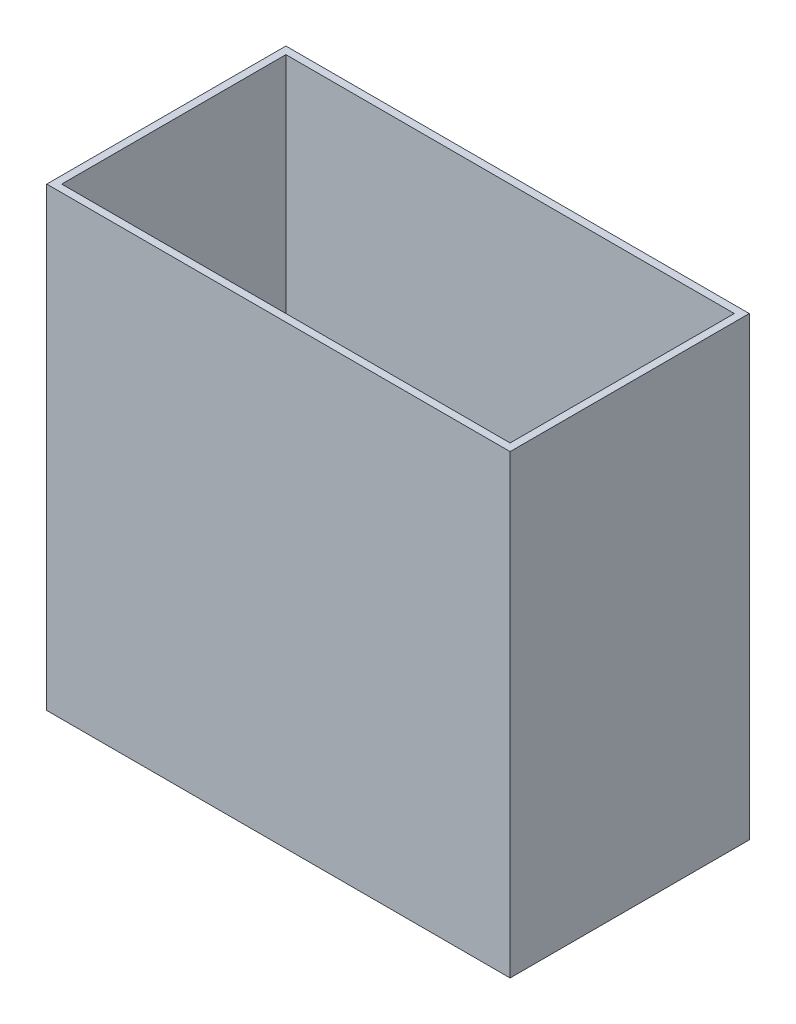
SolidWorks part; units mm, degrees
ref_plane "Plano frontal" through (0, 0, 0) normal (0, 0, 1) x (1, 0, 0)
ref_plane "Plano superior" through (0, 0, 0) normal (0, 1, 0) x (1, 0, 0)
ref_plane "Plano direito" through (0, 0, 0) normal (1, 0, 0) x (0, 0, -1)
sketch "Sketch1" plane through (0, 0, 0) normal (0, 0, 1) x (1, 0, 0)
  line L1 (30, 30) -> (-30, 30)
  line L2 (30, 30) -> (30, -30)
  line L3 (30, -30) -> (-30, -30)
  line L4 (-30, 30) -> (-30, -30)
  line L5 (30, 30) -> (-30, -30) construction
  line L6 (30, -30) -> (-30, 30) construction
  point P0 (0, 0)
  dimension "D1" = 60
  dimension "D2" = 60
extrude "Boss-Extrude1" add sketch "Sketch1" along normal blind 30
shell "Shell1" thickness 1 removed face at (0, 30, 15) outward yes
sketch "Sketch2" plane through (0, 0, 31) normal (0, 0, 1) x (1, 0, 0)
  circle A0 centre (0, 103.5816) radius 182.5
  dimension "D1" = 365
  dimension "D2" = 210
extrude "Cut-Extrude1" cut sketch "Sketch2" against normal through all rebuild error yes
